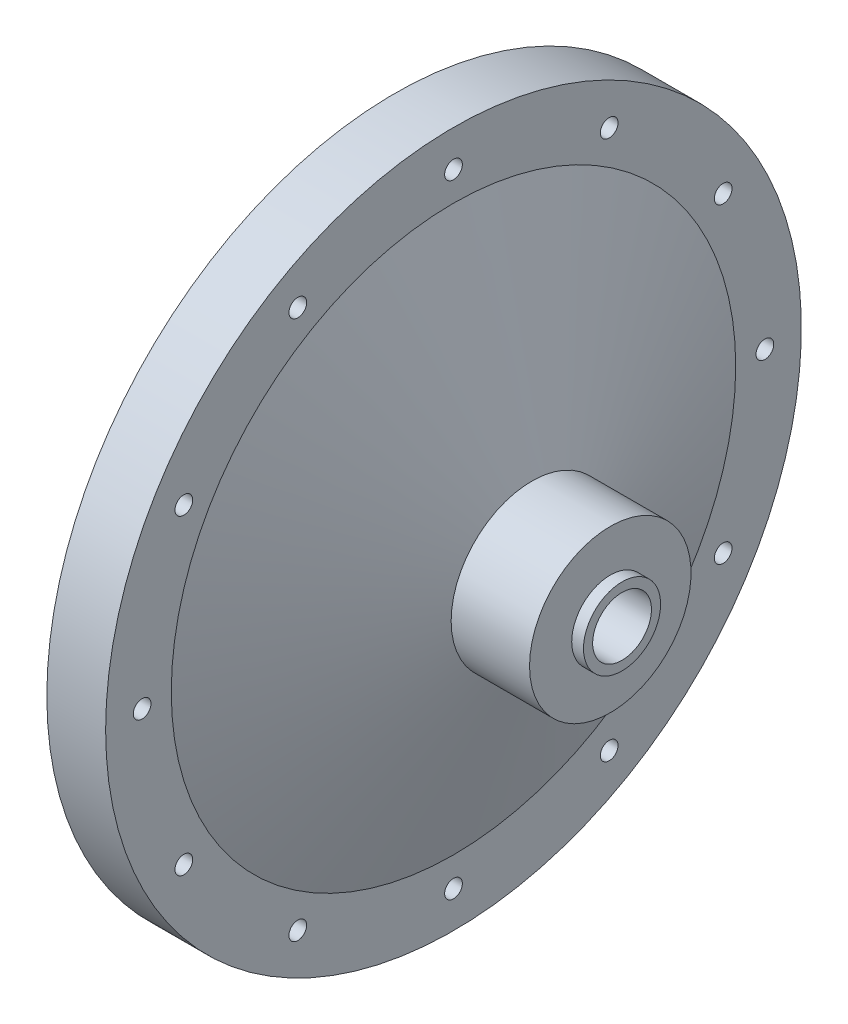
SolidWorks part; units mm, degrees
material "6061-T6 (SS)"
ref_plane "Front Plane" through (0, 0, 0) normal (0, 0, 1) x (1, 0, 0)
ref_plane "Top Plane" through (0, 0, 0) normal (0, 1, 0) x (1, 0, 0)
ref_plane "Right Plane" through (0, 0, 0) normal (1, 0, 0) x (0, 0, -1)
sketch "Sketch2" plane through (0, 0, 0) normal (0, 0, 1) x (1, 0, 0)
  line L0 (0, 0) -> (165.0115, 0) construction
  line L1 (0, 0) -> (0, 56.3562)
  line L2 (0, 56.3562) -> (9.525, 56.3562)
  line L3 (9.525, 56.3562) -> (9.525, 45.72)
  line L4 (9.525, 45.72) -> (22.225, 13.081)
  line L5 (34.925, 13.081) -> (34.925, 6.2484)
  line L6 (22.225, 13.081) -> (34.925, 13.081)
  line L7 (34.925, 6.2484) -> (36.83, 6.2484)
  line L8 (36.83, 6.2484) -> (36.83, 0)
  line L9 (0, 0) -> (36.83, 0)
  dimension "D1" = 56.3562
  dimension "D2" = 9.525
  dimension "D3" = 45.72
  dimension "D4" = 13.081
  dimension "D5" = 12.7
  dimension "D6" = 12.7
  dimension "D7" = 6.2484
  dimension "D8" = 1.905
revolve "Main Structure" add sketch "Sketch2" angle 360 about L0
cosmetic thread "Cosmetic Thread1" parameters "D2"=23.1953
sketch "Sketch3" plane through (36.83, 0, 0) normal (1, 0, 0) x (0, 0, -1)
  circle A0 centre (0, 0) radius 4.7625
  dimension "D1" = 9.525
extrude "Oxidizer Inlet Hole" cut sketch "Sketch3" against normal through all
sketch "Sketch4" plane through (0, 0, 0) normal (-1, 0, 0) x (0, 0, 1)
  circle A0 centre (0, 0) radius 50.4444 construction
  circle A1 centre (0, -50.4444) radius 2.146
  circle A2 centre (-25.2222, -43.6861) radius 2.146
  circle A3 centre (-43.6861, -25.2222) radius 2.146
  circle A4 centre (-50.4444, 0) radius 2.146
  circle A5 centre (-43.6861, 25.2222) radius 2.146
  circle A6 centre (-25.2222, 43.6861) radius 2.146
  circle A7 centre (0, 50.4444) radius 2.146
  circle A8 centre (25.2222, 43.6861) radius 2.146
  circle A9 centre (43.6861, 25.2222) radius 2.146
  circle A10 centre (50.4444, 0) radius 2.146
  circle A11 centre (43.6861, -25.2222) radius 2.146
  circle A12 centre (25.2222, -43.6861) radius 2.146
  point P29 (0, 0)
  dimension "D1" = 12
hole_wizard "Flange Holes" positions "Sketch7" profile "Sketch8" hole size "#33" standard "ANSI Inch"
sketch "Sketch7" plane through (0, 0, 0) normal (-1, 0, 0) x (0, 0, 1)
  point P0 (0, -50.4444)
  point P3 (-25.2222, -43.6861)
  point P6 (-43.6861, -25.2222)
  point P9 (-50.4444, 0)
  point P12 (-43.6861, 25.2222)
  point P15 (-25.2222, 43.6861)
  point P18 (0, 50.4444)
  point P21 (25.2222, 43.6861)
  point P24 (43.6861, 25.2222)
  point P27 (50.4444, 0)
  point P30 (43.6861, -25.2222)
  point P33 (25.2222, -43.6861)
sketch "Sketch8" plane through (0, -50.4444, 0) normal (0, 1, 0) x (0, 0, 1)
  line L0 (0, 0) -> (0, 26.2623)
  line L1 (0, 26.2623) -> (1.4351, 25.4)
  line L2 (1.4351, 25.4) -> (1.4351, 0)
  line L5 (1.4351, 0) -> (0, 0)
  line L10 (0, 26.2623) -> (-1.4351, 25.4) construction
  line L11 (0, -6.35) -> (0, 107.95) construction
  dimension "Hole Dia." = 2.8702
  dimension "Hole Depth" = 25.4
  dimension "Drill Angle" = 118
sketch "Sketch9" plane through (0, 0, 0) normal (-1, 0, 0) x (0, 0, 1)
  line L0 (0, 0) -> (-67.6727, 18.1329) construction
  line L1 (0, 0) -> (-50.4444, 0) construction
  circle A0 centre (0, 0) radius 50.4444 construction
  circle A1 centre (-48.7255, 13.056) radius 2.9451
  circle A2 centre (48.7255, -13.056) radius 2.9451
  point P14 (0, 0)
  dimension "D1" = 15
  dimension "D2" = 2
hole_wizard "Dowel Holes" positions "Sketch10" profile "Sketch11" hole size "3/16" standard "ANSI Inch"
sketch "Sketch10" plane through (0, 0, 0) normal (-1, 0, 0) x (0, 0, 1)
  point P0 (48.7255, -13.056)
  point P3 (-48.7255, 13.056)
sketch "Sketch11" plane through (0, -13.056, 48.7255) normal (0, 1, 0) x (0, 0, 1)
  line L0 (0, 0) -> (0, 7.7808)
  line L1 (0, 7.7808) -> (2.3812, 6.35)
  line L2 (2.3812, 6.35) -> (2.3812, 0)
  line L5 (2.3812, 0) -> (0, 0)
  line L10 (0, 7.7808) -> (-2.3812, 6.35) construction
  line L11 (0, -6.35) -> (0, 107.95) construction
  dimension "Hole Dia." = 4.7625
  dimension "Hole Depth" = 6.35
  dimension "Drill Angle" = 118
sketch "Sketch12" plane through (0, 0, 0) normal (-1, 0, 0) x (0, 0, 1)
  circle A0 centre (0, 0) radius 38.1
  dimension "D1" = 76.2
extrude "Impinging Plate Flat Cut" cut sketch "Sketch12" against normal blind 3.81
ref_plane "Plane1" through (6.35, 0, 0) normal (-1, 0, 0) x (0, 0, 1)
sketch "Sketch14" plane through (3.81, 0, 0) normal (-1, 0, 0) x (0, 0, 1)
  circle A0 centre (0, 0) radius 38.1
  dimension "D1" = 76.2
sketch "Sketch15" plane through (6.35, 0, 0) normal (-1, 0, 0) x (0, 0, 1)
  circle A0 centre (0, 0) radius 38.0873
  dimension "D1" = 76.1746
loft "Impinging Plate Taper Cut" cut profiles "Sketch14", "Sketch15" connector at (3.81, 0, 38.1) connector at (6.35, 0, 38.0873)
sketch "Sketch16" plane through (6.35, 0, 0) normal (-1, 0, 0) x (0, 0, 1)
  circle A0 centre (0, 0) radius 28.575
  dimension "D1" = 57.15
ref_plane "Plane2" through (21.59, 0, 0) normal (-1, 0, 0) x (0, 0, 1)
sketch "Sketch17" plane through (21.59, 0, 0) normal (-1, 0, 0) x (0, 0, 1)
  circle A0 centre (0, 0) radius 4.7625
  dimension "D1" = 9.525
loft "Internal Flow Path Loft Cut" cut profiles "Sketch16", "Sketch17" connector at (6.35, 0, 28.575) connector at (21.59, 0, 4.7625)
fillet "Internal Fillet" radius 3.175 1 edges at (21.59, 0, 4.7625)
sketch "Sketch18" plane through (6.35, 0, 0) normal (-1, 0, 0) x (0, 0, 1)
  circle A0 centre (0, 0) radius 33.3375
  circle A1 centre (33.3375, 0) radius 1.5042
  dimension "D1" = 66.675
hole_wizard "4-40 Tapped Holes " positions "Sketch19" profile "Sketch20" hole size "#4-40" standard "ANSI Inch"
sketch "Sketch19" plane through (6.35, 0, 0) normal (-1, 0, 0) x (0, 0, 1)
  point P0 (33.3375, 0)
sketch "Sketch20" plane through (6.35, 0, 33.3375) normal (0, 1, 0) x (0, 0, 1)
  line L0 (0, 0) -> (0, 7.0292)
  line L1 (0, 7.0292) -> (1.1303, 6.35)
  line L2 (1.1303, 6.35) -> (1.1303, 0)
  line L5 (1.1303, 0) -> (0, 0)
  line L10 (0, 7.0292) -> (-1.1303, 6.35) construction
  line L11 (0, -6.35) -> (0, 107.95) construction
  dimension "Hole Dia." = 2.2606
  dimension "Hole Depth" = 6.35
  dimension "Drill Angle" = 118
pattern_circular "Extended 8 BC" count 8 over 360 about axis through (3.81, 0, 0) along (-1, 0, 0) of "4-40 Tapped Holes "
chamfer "Chamfer for Impinging Edge" distance 0.127 angle 45 1 edges at (6.35, 0, 38.0873) first distance on face at (3.81, 0, 38.1)
